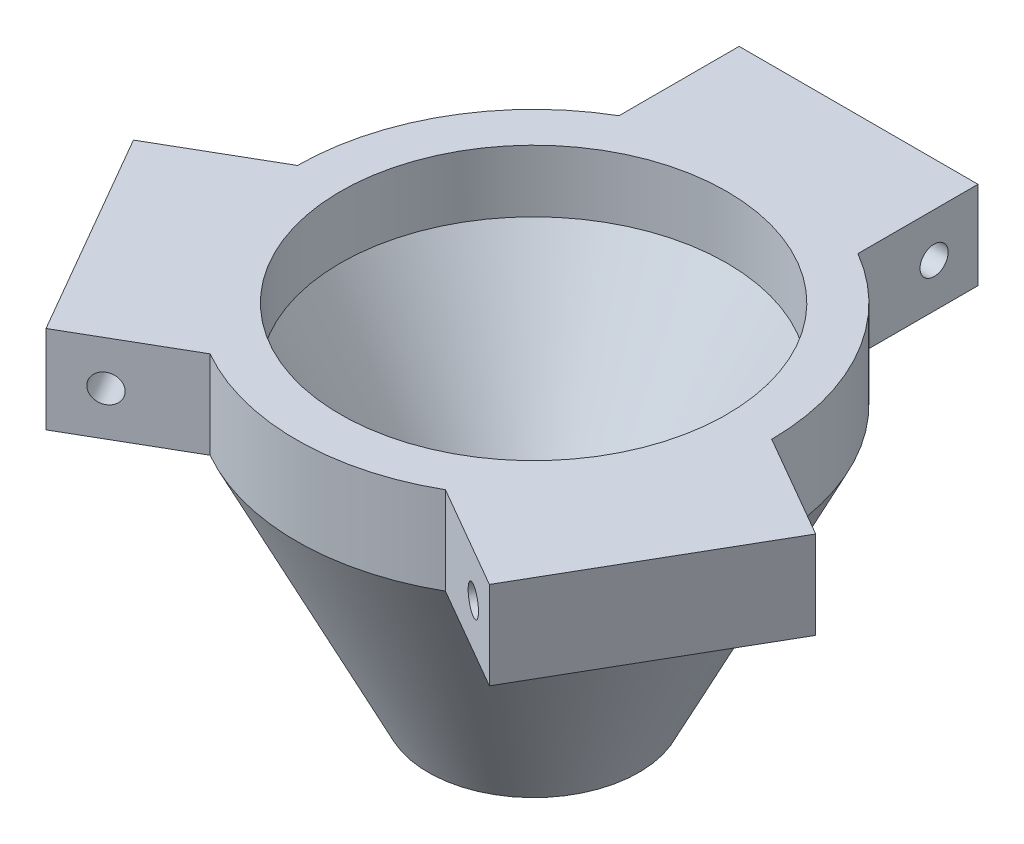
SolidWorks part; units mm, degrees
ref_plane "Plan de face" through (0, 0, 0) normal (0, 0, 1) x (1, 0, 0)
ref_plane "Plan de dessus" through (0, 0, 0) normal (0, 1, 0) x (1, 0, 0)
ref_plane "Plan de droite" through (0, 0, 0) normal (1, 0, 0) x (0, 0, -1)
sketch "Esquisse1" plane through (0, 0, 0) normal (0, 0, 1) x (1, 0, 0)
  line L0 (0, 0) -> (0, 25.9795) construction
  line L1 (-6, 0) -> (-12, 0)
  line L2 (-12, 0) -> (-27, 30.3)
  line L3 (-27, 30.3) -> (-27, 40.3)
  line L4 (-27, 40.3) -> (-22, 40.3)
  line L5 (-6, 0) -> (-6, 7.2548)
  line L6 (-6, 7.2548) -> (-22, 33.2372)
  line L7 (-22, 33.2372) -> (-22, 40.3)
  dimension "D1" = 6
  dimension "D2" = 40.3
  dimension "D3" = 27
  dimension "D4" = 5
  dimension "D5" = 6
  dimension "D6" = 10
revolve "Révolution1" add sketch "Esquisse1" angle 360 about L0
sketch "Esquisse2" plane through (0, 40.3, 0) normal (0, 1, 0) x (1, 0, 0)
  line L0 (0, 0) -> (0, 35.8531) construction
  line L1 (-13.6, 37) -> (13.6, 37)
  line L2 (-13.6, 37) -> (-13.6, 22.9827)
  line L3 (-13.6, 22.9827) -> (13.6, 22.9827)
  line L4 (13.6, 37) -> (13.6, 22.9827)
  dimension "D1" = 27.2
  dimension "D2" = 13.6
  dimension "D3" = 37
extrude "Boss.-Extru.1" add sketch "Esquisse2" against normal blind 10
sketch "Esquisse3" plane through (-13.6, 0, 0) normal (-1, 0, 0) x (0, 0, 1)
  line L0 (0, 30.3) -> (0, 0) construction
  line L1 (-37, 30.3) -> (-23.3247, 30.3) construction
  circle A0 centre (-32, 35.3) radius 1.6
  dimension "D1" = 3.2
  dimension "D3" = 5
  dimension "D2" = 32
extrude "Enlèv. mat.-Extru.1" cut sketch "Esquisse3" against normal through all
pattern_circular "Répétition circulaire1" count 3 over 360 about axis through (0, 30.3, 0) along (0, -1, 0) of "Boss.-Extru.1", "Enlèv. mat.-Extru.1"
ref_axis "Axe1" through (0, 30.3, 0) along (0, -1, 0)
ref_point "Point1"
